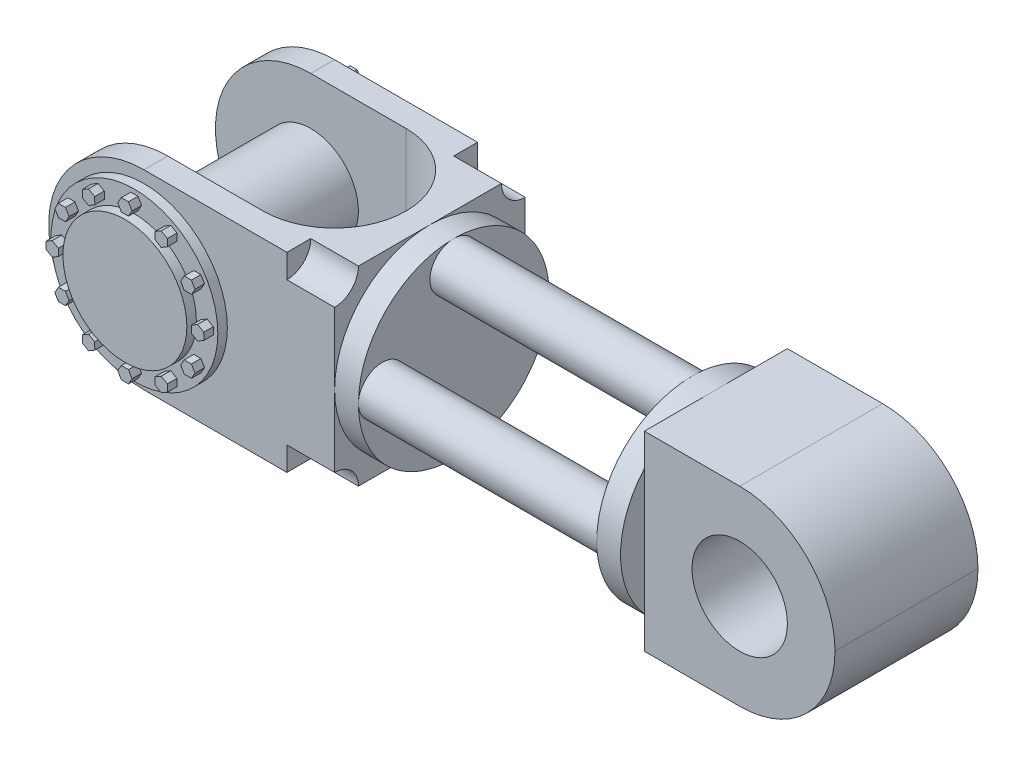
SolidWorks part; units mm, degrees
ref_plane "Front Plane" through (0, 0, 0) normal (0, 0, 1) x (1, 0, 0)
ref_plane "Top Plane" through (0, 0, 0) normal (0, 1, 0) x (1, 0, 0)
ref_plane "Right Plane" through (0, 0, 0) normal (1, 0, 0) x (0, 0, -1)
sketch "Sketch1" plane through (0, 0, 0) normal (0, 0, 1) x (1, 0, 0)
  line L0 (0, 0) -> (-40, 0) construction
  line L1 (-40, 20) -> (0, 20)
  line L2 (-40, -20) -> (0, -20)
  line L3 (0, -20) -> (0, 20)
  arc A0 (-40, 20) -> (-40, -20) centre (-40, 0) ccw
extrude "Boss-Extrude1" add sketch "Sketch1" along normal blind 20
sketch "Sketch2" plane through (0, 0, 20) normal (0, 0, 1) x (1, 0, 0)
  line L0 (-40, 20) -> (-40, -20) construction
  circle A0 centre (-40, 0) radius 17.5
extrude "Boss-Extrude2" add sketch "Sketch2" along normal blind 2
sketch "Sketch3" plane through (0, 0, 22) normal (0, 0, 1) x (1, 0, 0)
  circle A0 centre (-40, 0) radius 13
extrude "Boss-Extrude3" add sketch "Sketch3" along normal blind 2
sketch "Sketch5" plane through (0, 0, 22) normal (0, 0, 1) x (1, 0, 0)
  line L1 (-40, 17.5) -> (-40, 13) construction
  line L2 (-39.2424, 13.9554) -> (-38.5, 15.2588)
  line L3 (-38.5, 15.2588) -> (-39.2576, 16.5534)
  line L4 (-39.2576, 16.5534) -> (-40.7576, 16.5446)
  line L5 (-40.7576, 16.5446) -> (-41.5, 15.2412)
  line L6 (-41.5, 15.2412) -> (-40.7424, 13.9466)
  line L7 (-40.7424, 13.9466) -> (-39.2424, 13.9554)
  circle A0 centre (-40, 0) radius 17.5 construction
  circle A1 centre (-40, 0) radius 13 construction
  circle A2 centre (-40, 15.25) radius 1.299 construction
  dimension "D1" = 1.5
extrude "Boss-Extrude5" add sketch "Sketch5" along normal blind 2
pattern_circular "CirPattern1" count 12 every 30 about axis through (-40, 0, 24) along (0, 0, 1) of "Boss-Extrude5"
sketch "Sketch6" plane through (0, 20, 0) normal (0, 1, 0) x (1, 0, 0)
  line L0 (-40, 0) -> (-20, 0) construction
  line L1 (0, 0) -> (-40, 0) construction
  line L2 (-20, -15) -> (-65, -15)
  line L3 (-65, -15) -> (-65, 5)
  line L4 (-65, 5) -> (-5.8579, 5)
  arc A0 (-20, -15) -> (-5.8579, 5) centre (-20, 0) ccw
extrude "Cut-Extrude1" cut sketch "Sketch6" against normal blind 50
sketch "Sketch7" plane through (0, 0, 15) normal (0, 0, -1) x (-1, 0, 0)
  line L0 (40, 20) -> (40, -20) construction
  circle A0 centre (40, 0) radius 10
mirror "Mirror1" about plane through (0, 0, 0) normal (0, 0, 1) of "Boss-Extrude5", "CirPattern1", "Boss-Extrude3", "Boss-Extrude2", "Cut-Extrude1", "Boss-Extrude1"
extrude "Boss-Extrude6" add sketch "Sketch7" along normal blind 30 contours A0
sketch "Sketch8" plane through (0, 0, 0) normal (1, 0, 0) x (0, 0, -1)
  line L0 (-20, 20) -> (20, -20) construction
  circle A0 centre (0, 0) radius 20
extrude "Boss-Extrude7" add sketch "Sketch8" along normal blind 5 contours A0
sketch "Sketch9" plane through (0, 0, 0) normal (1, 0, 0) x (0, 0, -1)
  circle A0 centre (-20, 20) radius 5
extrude "Cut-Extrude2" cut sketch "Sketch9" against normal blind 10
pattern_circular "CirPattern2" count 4 every 90 about axis through (5, 0, 0) along (1, 0, 0) of "Cut-Extrude2"
sketch "Sketch11" plane through (5, 0, 0) normal (1, 0, 0) x (0, 0, -1)
  line L0 (0, 20) -> (0, 10) construction
  circle A0 centre (0, 0) radius 20 construction
  circle A1 centre (0, 15) radius 5
extrude "Boss-Extrude10" add sketch "Sketch11" along normal blind 50
pattern_circular "CirPattern4" count 4 every 90 about axis through (5, 0, 0) along (1, 0, 0) of "Boss-Extrude10"
sketch "Sketch13" plane through (55, 0, 0) normal (1, 0, 0) x (0, 0, -1)
  line L0 (0, 20) -> (0, -20) construction
  circle A0 centre (0, 0) radius 20
extrude "Boss-Extrude11" add sketch "Sketch13" along normal blind 5
sketch "Sketch14" plane through (60, 0, 0) normal (1, 0, 0) x (0, 0, -1)
  line L0 (0, -20) -> (15, -20) construction
  line L1 (-15, 20) -> (15, 20)
  line L2 (-15, 20) -> (-15, -20)
  line L3 (-15, -20) -> (15, -20)
  line L4 (15, 20) -> (15, -20)
  line L5 (-15, 20) -> (15, -20) construction
  line L6 (-15, -20) -> (15, 20) construction
  point P0 (0, 0)
  dimension "D1" = 30
extrude "Boss-Extrude12" add sketch "Sketch14" along normal blind 40
sketch "Sketch15" plane through (0, 0, 15) normal (0, 0, 1) x (1, 0, 0)
  line L0 (60, 20) -> (100, -20) construction
  circle A0 centre (80, 0) radius 10
extrude "Cut-Extrude3" cut sketch "Sketch15" against normal blind 40
fillet "Fillet1" radius 20 2 edges at (100, -20, 0) (100, 20, 0)
sketch "Sketch16" plane through (0, 0, 0) normal (0, 0, 1) x (1, 0, 0)
  point P0 (80, 0)
move or copy body "Body-Move/Copy1" bodies to move or copy 120 copy no translate (-80, 0, 0)
